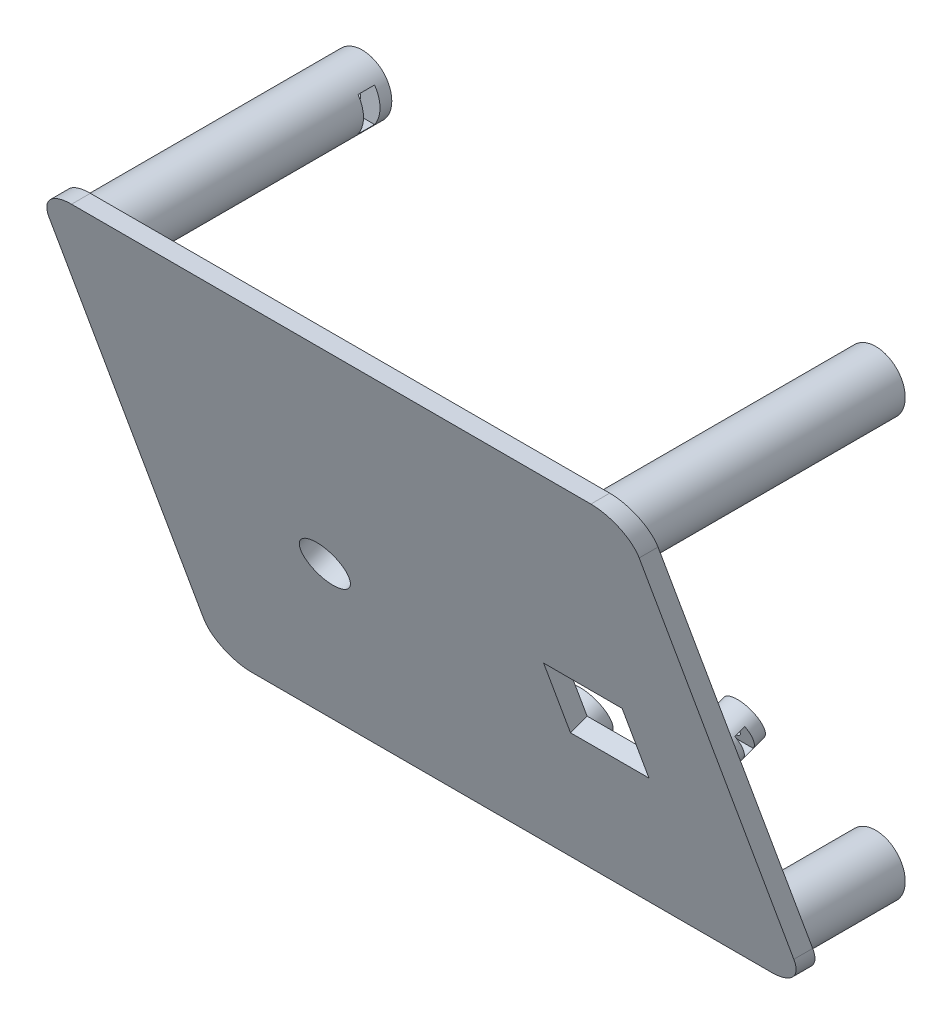
SolidWorks part; units mm, degrees
ref_plane "前视基准面" through (0, 0, 0) normal (0, 0, 1) x (1, 0, 0)
ref_plane "上视基准面" through (0, 0, 0) normal (0, 1, 0) x (1, 0, 0)
ref_plane "右视基准面" through (0, 0, 0) normal (1, 0, 0) x (0, 0, -1)
other "Configuration Table"
sketch "草图1" plane through (0, 0, 0) normal (0, 0, 1) x (1, 0, 0)
  line L0 (6, 0) -> (94, 0)
  line L1 (100, 6) -> (100, 78)
  line L2 (94, 84) -> (6, 84)
  line L3 (0, 78) -> (0, 6)
  arc A0 (94, 0) -> (100, 6) centre (94, 6) ccw
  arc A1 (100, 78) -> (94, 84) centre (94, 78) ccw
  arc A2 (6, 84) -> (0, 78) centre (6, 78) ccw
  arc A3 (0, 6) -> (6, 0) centre (6, 6) ccw
extrude "Lid_blank" add sketch "草图1" along normal blind 56
sketch "草图2" plane through (0, 0, 0) normal (1, 0, 0) x (0, 0, -1)
  line L0 (-13.9131, -20) -> (-61.2293, 110)
  line L1 (-61.2293, 110) -> (-120, 110)
  line L2 (-120, 110) -> (-120, -20)
  line L3 (-120, -20) -> (-13.9131, -20)
extrude "Outer_panel_20deg" cut sketch "草图2" against normal through all and the other way through all
sketch "草图3" plane through (0, 0, 0) normal (1, 0, 0) x (0, 0, -1)
  line L0 (-10.7206, -20) -> (-58.0367, 110)
  line L1 (-58.0367, 110) -> (30, 110)
  line L2 (30, 110) -> (30, -20)
  line L3 (30, -20) -> (-10.7206, -20)
extrude "Panel_3mm" cut sketch "草图3" against normal through all and the other way through all
sketch "草图4" plane through (0, 0, 0) normal (0, 0, 1) x (1, 0, 0)
  circle A0 centre (6.5, 6.5) radius 5
extrude "Hidden_case_post_0" add sketch "草图4" along normal blind 22.8782 from offset 3
sketch "草图5" plane through (0, 0, 0) normal (0, 0, 1) x (1, 0, 0)
  circle A0 centre (93.5, 6.5) radius 5
extrude "Hidden_case_post_1" add sketch "草图5" along normal blind 22.8782 from offset 3
sketch "草图6" plane through (0, 0, 0) normal (0, 0, 1) x (1, 0, 0)
  circle A0 centre (6.5, 77.5) radius 5
extrude "Hidden_case_post_2" add sketch "草图6" along normal blind 48.7201 from offset 3
sketch "草图7" plane through (0, 0, 0) normal (0, 0, 1) x (1, 0, 0)
  circle A0 centre (93.5, 77.5) radius 5
extrude "Hidden_case_post_3" add sketch "草图7" along normal blind 48.7201 from offset 3
sketch "草图8" plane through (0, 0, 0) normal (1, 0, 0) x (0, 0, -1)
  line L0 (-13.9131, -20) -> (-61.2293, 110)
  line L1 (-61.2293, 110) -> (-120, 110)
  line L2 (-120, 110) -> (-120, -20)
  line L3 (-120, -20) -> (-13.9131, -20)
extrude "Flush_outer_surface" cut sketch "草图8" against normal through all and the other way through all
sketch "草图9" plane through (0, 0, 0) normal (0, 0, 1) x (1, 0, 0)
  circle A0 centre (6.5, 6.5) radius 1.7
extrude "Blind_M3_0" cut sketch "草图9" along normal blind 9.5 from offset 3
sketch "草图10" plane through (0, 0, 0) normal (1, 0, 0) x (0, 0, -1)
  line L0 (-5, 3.6) -> (-5, 9.4)
  line L1 (-5, 9.4) -> (-7.8, 9.4)
  line L2 (-7.8, 9.4) -> (-7.8, 3.6)
  line L3 (-7.8, 3.6) -> (-5, 3.6)
extrude "M3_side_load_nut_0" cut sketch "草图10" along normal blind 9.4 from offset 3.1
sketch "草图11" plane through (0, 0, 0) normal (0, 0, 1) x (1, 0, 0)
  circle A0 centre (93.5, 6.5) radius 1.7
extrude "Blind_M3_1" cut sketch "草图11" along normal blind 9.5 from offset 3
sketch "草图12" plane through (0, 0, 0) normal (1, 0, 0) x (0, 0, -1)
  line L0 (-5, 3.6) -> (-5, 9.4)
  line L1 (-5, 9.4) -> (-7.8, 9.4)
  line L2 (-7.8, 9.4) -> (-7.8, 3.6)
  line L3 (-7.8, 3.6) -> (-5, 3.6)
extrude "M3_side_load_nut_1" cut sketch "草图12" along normal blind 9.4 from offset 87.5
sketch "草图13" plane through (0, 0, 0) normal (0, 0, 1) x (1, 0, 0)
  circle A0 centre (6.5, 77.5) radius 1.7
extrude "Blind_M3_2" cut sketch "草图13" along normal blind 9.5 from offset 3
sketch "草图14" plane through (0, 0, 0) normal (1, 0, 0) x (0, 0, -1)
  line L0 (-5, 74.6) -> (-5, 80.4)
  line L1 (-5, 80.4) -> (-7.8, 80.4)
  line L2 (-7.8, 80.4) -> (-7.8, 74.6)
  line L3 (-7.8, 74.6) -> (-5, 74.6)
extrude "M3_side_load_nut_2" cut sketch "草图14" along normal blind 9.4 from offset 3.1
sketch "草图15" plane through (0, 0, 0) normal (0, 0, 1) x (1, 0, 0)
  circle A0 centre (93.5, 77.5) radius 1.7
extrude "Blind_M3_3" cut sketch "草图15" along normal blind 9.5 from offset 3
sketch "草图16" plane through (0, 0, 0) normal (1, 0, 0) x (0, 0, -1)
  line L0 (-5, 74.6) -> (-5, 80.4)
  line L1 (-5, 80.4) -> (-7.8, 80.4)
  line L2 (-7.8, 80.4) -> (-7.8, 74.6)
  line L3 (-7.8, 74.6) -> (-5, 74.6)
extrude "M3_side_load_nut_3" cut sketch "草图16" along normal blind 9.4 from offset 87.5
sketch "草图17" plane through (0, -6.8111, 18.7135) normal (0, -0.342, 0.9397) x (1, 0, 0)
  circle A0 centre (31, 44.2483) radius 4.1
extrude "Shaft_D8p2" cut sketch "草图17" against normal blind 5
sketch "草图18" plane through (0, -6.8111, 18.7135) normal (0, -0.342, 0.9397) x (1, 0, 0)
  line L0 (70.35, 37.5983) -> (83.65, 37.5983)
  line L1 (83.65, 37.5983) -> (83.65, 50.8983)
  line L2 (83.65, 50.8983) -> (70.35, 50.8983)
  line L3 (70.35, 50.8983) -> (70.35, 37.5983)
extrude "Button_13p3_clearance" cut sketch "草图18" against normal blind 5
sketch "草图19" plane through (0, -5.7851, 15.8944) normal (0, 0.342, -0.9397) x (-1, 0, 0)
  circle A0 centre (-23, 30.7483) radius 4
extrude "Encoder_front_blind_post" add sketch "草图19" along normal blind 11.07
sketch "草图20" plane through (0, -6.8111, 18.7135) normal (0, -0.342, 0.9397) x (1, 0, 0)
  circle A0 centre (23, 30.7483) radius 1.15
extrude "Encoder_front_blind_screw" cut sketch "草图20" along normal blind 5 from offset 14.07 offset against normal yes
sketch "草图21" plane through (0, 0, 0) normal (1, 0, 0) x (0, 0, -1)
  line L0 (-17.1697, 24.2376) -> (-18.6062, 28.1843)
  line L1 (-18.6062, 28.1843) -> (-20.2976, 27.5687)
  line L2 (-20.2976, 27.5687) -> (-18.8611, 23.622)
  line L3 (-18.8611, 23.622) -> (-17.1697, 24.2376)
extrude "Encoder_front_M2_side_nut" cut sketch "草图21" along normal blind 7.5 from offset 20.5
sketch "草图22" plane through (0, -5.7851, 15.8944) normal (0, 0.342, -0.9397) x (-1, 0, 0)
  circle A0 centre (-47, 57.7483) radius 4
extrude "Encoder_rear_blind_post" add sketch "草图22" along normal blind 11.07
sketch "草图23" plane through (0, -6.8111, 18.7135) normal (0, -0.342, 0.9397) x (1, 0, 0)
  circle A0 centre (47, 57.7483) radius 1.15
extrude "Encoder_rear_blind_screw" cut sketch "草图23" along normal blind 5 from offset 14.07 offset against normal yes
sketch "草图24" plane through (0, 0, 0) normal (1, 0, 0) x (0, 0, -1)
  line L0 (-26.4042, 49.6093) -> (-27.8407, 53.556)
  line L1 (-27.8407, 53.556) -> (-29.5321, 52.9404)
  line L2 (-29.5321, 52.9404) -> (-28.0957, 48.9937)
  line L3 (-28.0957, 48.9937) -> (-26.4042, 49.6093)
extrude "Encoder_rear_M2_side_nut" cut sketch "草图24" along normal blind 7.5 from offset 44.5
sketch "草图25" plane through (0, -5.7851, 15.8944) normal (0, 0.342, -0.9397) x (-1, 0, 0)
  circle A0 centre (-60, 25.2483) radius 4
extrude "Button_left_blind_post" add sketch "草图25" along normal blind 6.7
sketch "草图26" plane through (0, -6.8111, 18.7135) normal (0, -0.342, 0.9397) x (1, 0, 0)
  circle A0 centre (60, 25.2483) radius 1.15
extrude "Button_left_blind_screw" cut sketch "草图26" along normal blind 5 from offset 9.7 offset against normal yes
sketch "草图27" plane through (0, 0, 0) normal (1, 0, 0) x (0, 0, -1)
  line L0 (-19.395, 17.5747) -> (-20.8315, 21.5214)
  line L1 (-20.8315, 21.5214) -> (-22.523, 20.9057)
  line L2 (-22.523, 20.9057) -> (-21.0865, 16.959)
  line L3 (-21.0865, 16.959) -> (-19.395, 17.5747)
extrude "Button_left_M2_side_nut" cut sketch "草图27" along normal blind 7.5 from offset 57.5
sketch "草图28" plane through (0, -5.7851, 15.8944) normal (0, 0.342, -0.9397) x (-1, 0, 0)
  circle A0 centre (-93.3, 45.2483) radius 3.4
extrude "Button_right_blind_post" add sketch "草图28" along normal blind 6.7
sketch "草图29" plane through (0, -6.8111, 18.7135) normal (0, -0.342, 0.9397) x (1, 0, 0)
  circle A0 centre (93.3, 45.2483) radius 1.15
extrude "Button_right_blind_screw" cut sketch "草图29" along normal blind 5 from offset 9.7 offset against normal yes
sketch "草图30" plane through (0, 0, 0) normal (1, 0, 0) x (0, 0, -1)
  line L0 (-26.2354, 36.3685) -> (-27.6719, 40.3152)
  line L1 (-27.6719, 40.3152) -> (-29.3634, 39.6996)
  line L2 (-29.3634, 39.6996) -> (-27.9269, 35.7529)
  line L3 (-27.9269, 35.7529) -> (-26.2354, 36.3685)
extrude "Button_right_M2_side_nut" cut sketch "草图30" along normal blind 7.5 from offset 90.8
